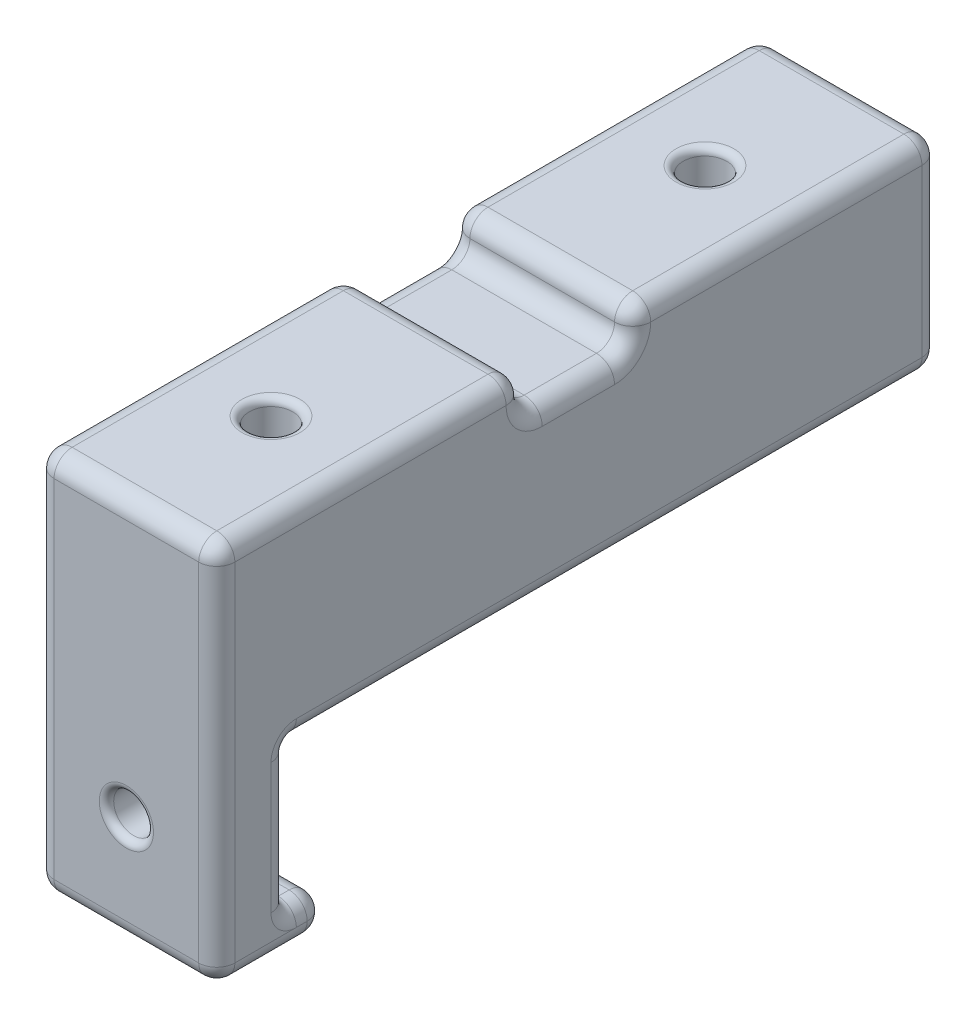
SolidWorks part; units mm, degrees
ref_plane "前视基准面" through (0, 0, 0) normal (0, 0, 1) x (1, 0, 0)
ref_plane "上视基准面" through (0, 0, 0) normal (0, 1, 0) x (1, 0, 0)
ref_plane "右视基准面" through (0, 0, 0) normal (1, 0, 0) x (0, 0, -1)
sketch "草图1" plane through (0, 0, 0) normal (0, 1, 0) x (1, 0, 0)
  line L0 (34.1897, 0) -> (59.1897, 0)
  line L1 (59.1897, 0) -> (59.1897, 100)
  line L2 (59.1897, 100) -> (34.1897, 100)
  line L3 (34.1897, 100) -> (34.1897, 0)
extrude "凸台-拉伸1" add sketch "草图1" along normal blind 28
sketch "草图2" plane through (0, 28, 0) normal (0, 1, 0) x (1, 0, 0)
  circle A0 centre (46.6897, 80) radius 3
  circle A1 centre (46.6897, 20) radius 3
extrude "切除-拉伸1" cut sketch "草图2" against normal through all
sketch "草图3" plane through (59.1897, 0, 0) normal (1, 0, 0) x (0, 0, -1)
  line L0 (23, 28) -> (17, 28) construction
  line L1 (23, 28) -> (17, 28)
  line L3 (0, 0) -> (100, 0) construction
  line L4 (10, 0) -> (10, -20)
  line L5 (10, -20) -> (0, -20)
  line L6 (0, -20) -> (0, 0)
  line L7 (0, 0) -> (10, 0)
  line M1 (0, 0) -> (100, 0)
extrude "凸台-拉伸2" add sketch "草图3" against normal up to surface (25 mm away) contours L6 L5 L4 M1 up to face at (34.1897, 14, -50)
sketch "草图4" plane through (0, 0, 0) normal (0, 0, 1) x (1, 0, 0)
  circle A0 centre (46.6897, -10) radius 2.75
extrude "切除-拉伸2" cut sketch "草图4" against normal through all
sketch "草图5" plane through (0, 0, 0) normal (0, 0, 1) x (1, 0, 0)
  line L0 (34.1897, -20) -> (59.1897, -20)
  line L1 (59.1897, -20) -> (59.1897, -25)
  line L2 (59.1897, -25) -> (34.1897, -25)
  line L3 (34.1897, -25) -> (34.1897, -20)
extrude "凸台-拉伸3" add sketch "草图5" against normal blind 15
sketch "草图6" plane through (0, 0, 0) normal (0, -1, 0) x (1, 0, 0)
  circle A0 centre (46.6897, -20) radius 6.5
  circle A1 centre (46.6897, -80) radius 6.5
extrude "切除-拉伸3" cut sketch "草图6" against normal blind 18
fillet "圆角1" radius 1 10 edges at (46.6897, -20, -10) (46.6897, 0, -10) (49.4397, -10, -10) (49.4397, -10, 0) (46.6897, 18, -83) (46.6897, 28, -77) (46.6897, 18, -23) (46.6897, 28, -17) (46.6897, 18, -26.5) (46.6897, 18, -86.5)
fillet "圆角2" radius 2.5 26 edges at (46.6897, -25, 0) (46.6897, -25, -15) (46.6897, -20, -15) (59.1897, -0.2929, -10.2929) (59.1897, -10, -10) (34.1897, -10, -10) (59.1897, -19.7071, -10.2929) (59.1897, -20, -13) (59.1897, -25, -7.5) (59.1897, 1.5, 0) (34.1897, 1.5, 0) (34.1897, -25, -7.5) (34.1897, -20, -13) (34.1897, -19.7071, -10.2929) (34.1897, -0.2929, -10.2929) (59.1897, 14, -100) (34.1897, 14, -100) (46.6897, 28, -100) (59.1897, 28, -50) (46.6897, 28, 0) (34.1897, 28, -50) (46.6897, 0, -100) (34.1897, 0, -55.5) (59.1897, 0, -55.5) (46.6897, 0, -86.5) (46.6897, 0, -26.5)
sketch "草图7" plane through (0, 28, 0) normal (0, 1, 0) x (1, 0, 0)
  line L0 (34.1897, 50) -> (34.1897, 57.5)
  line L1 (34.1897, 2.5) -> (34.1897, 97.5) construction
  line L2 (34.1897, 57.5) -> (59.1897, 57.5)
  line L3 (59.1897, 97.5) -> (59.1897, 2.5) construction
  line L4 (59.1897, 57.5) -> (59.1897, 42.5)
  line L5 (59.1897, 42.5) -> (34.1897, 42.5)
  line L6 (34.1897, 42.5) -> (34.1897, 50)
extrude "切除-拉伸4" cut sketch "草图7" against normal blind 5
fillet "圆角3" radius 2.5 10 edges at (46.6897, 28, -57.5) (46.6897, 28, -42.5) (58.4574, 27.2678, -57.5) (34.9219, 27.2678, -57.5) (58.4574, 27.2678, -42.5) (34.9219, 27.2678, -42.5) (46.6897, 23, -57.5) (59.1897, 23, -50) (46.6897, 23, -42.5) (34.1897, 23, -50)
